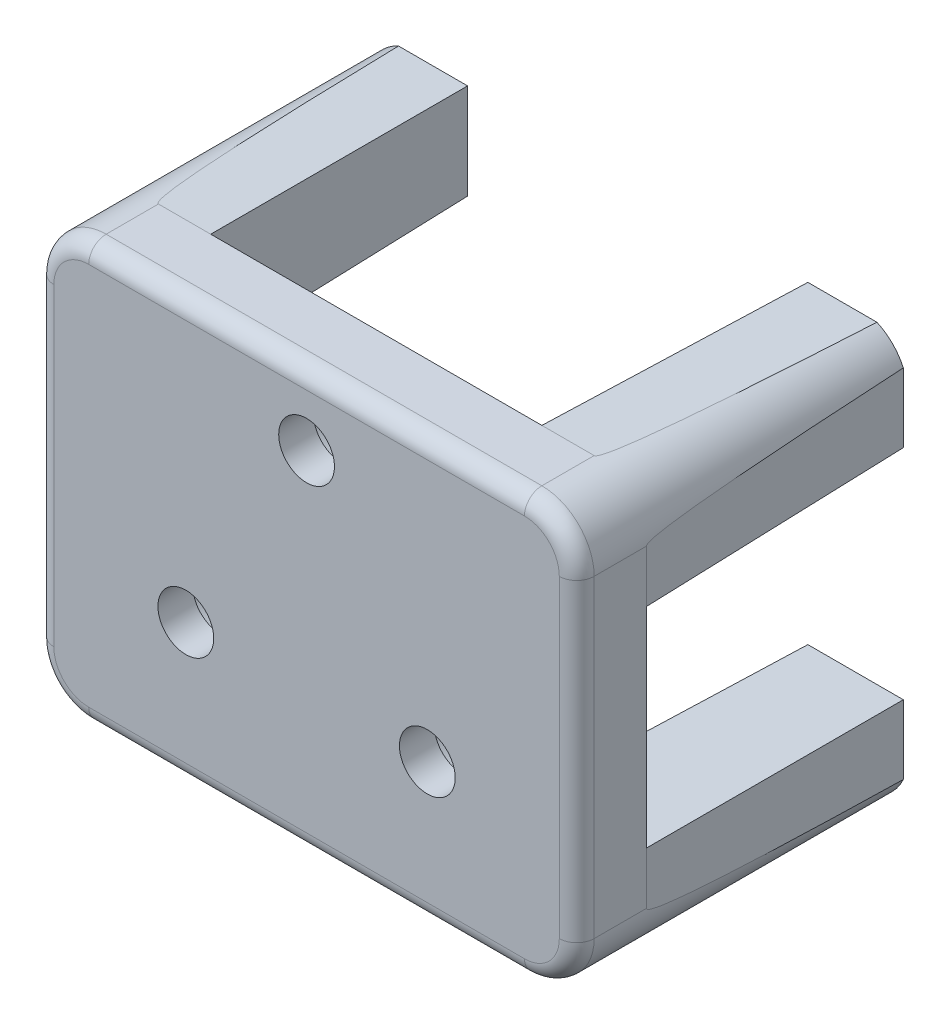
SolidWorks part; units mm, degrees
ref_plane "Front Plane" through (0, 0, 0) normal (0, 0, 1) x (1, 0, 0)
ref_plane "Top Plane" through (0, 0, 0) normal (0, 1, 0) x (1, 0, 0)
ref_plane "Right Plane" through (0, 0, 0) normal (1, 0, 0) x (0, 0, -1)
sketch "Sketch1" plane through (0, 0, 0) normal (0, 0, 1) x (1, 0, 0)
  line L1 (0, 0) -> (31, 0)
  line L2 (0, 0) -> (0, 24)
  line L3 (0, 24) -> (31, 24)
  line L4 (31, 0) -> (31, 24)
  line L5 (0, 24) -> (6, 24)
  line L6 (0, 24) -> (0, 18)
  line L7 (0, 18) -> (6, 18)
  line L8 (6, 24) -> (6, 18)
  line L9 (31, 24) -> (25, 24)
  line L10 (31, 24) -> (31, 18)
  line L11 (31, 18) -> (25, 18)
  line L12 (25, 24) -> (25, 18)
  line L13 (31, 0) -> (25, 0)
  line L14 (31, 0) -> (31, 6)
  line L15 (31, 6) -> (25, 6)
  line L16 (25, 0) -> (25, 6)
  line L17 (0, 0) -> (6, 0)
  line L18 (0, 0) -> (0, 6)
  line L19 (0, 6) -> (6, 6)
  line L20 (6, 0) -> (6, 6)
  dimension "D1" = 24
  dimension "D2" = 31
  dimension "D3" = 6
extrude "Boss-Extrude1" add sketch "Sketch1" along normal blind 4 contours L20 L1 L16 L15 L4 L11 L12 L3 L8 L7 L2 L19 | L8 L3 L2 L7 | L1 L20 L19 L2 | L3 L12 L11 L4 | L16 L1 L4 L15 region at (3, 3, 0) region at (15.5, 12, 0) region at (28, 3, 0) region at (3, 21, 0) region at (28, 21, 0)
extrude "Boss-Extrude2" add sketch "Sketch1<3>" against normal blind 15 draft 1 contours L8 L3 L2 L7 | L3 L12 L11 L4 | L16 L1 L4 L15 | L1 L20 L19 L2 region at (3, 3, 0) region at (28, 3, 0) region at (3, 21, 0) region at (28, 21, 0)
sketch "Sketch1<3>" plane through (0, 0, 0) normal (0, 0, 1) x (1, 0, 0) same geometry as "Sketch1"
sketch "Sketch2" plane through (0, 0, 0) normal (0, 0, -1) x (-1, 0, 0)
  line L0 (0, 6) -> (0, 18) construction
  line L1 (-6, 24) -> (-25, 24) construction
  line L2 (-15.5, 20) -> (-8.5718, 8) construction
  line L3 (-8.5718, 8) -> (-22.4282, 8) construction
  line L4 (-22.4282, 8) -> (-15.5, 20) construction
  line L5 (-6, 0) -> (-25, 0) construction
  circle A0 centre (-15.5, 12) radius 4 construction
  circle A1 centre (-22.4282, 8) radius 1.6
  circle A2 centre (-15.5, 20) radius 1.6
  circle A3 centre (-8.5718, 8) radius 1.6
  point P2 (-18.9641, 14)
  point P5 (0, 12)
  point P8 (-15.5, 24)
  point P12 (-12.0359, 14)
  point P13 (-15.5, 8)
  dimension "D1" = 8
  dimension "D2" = 3.2
extrude "Cut-Extrude1" cut sketch "Sketch2" against normal through all
sketch "Sketch3" plane through (0, 0, 0) normal (0, 0, -1) x (-1, 0, 0)
  circle A0 centre (-15.5, 20) radius 3
  circle A1 centre (-8.5718, 8) radius 3
  circle A2 centre (-22.4282, 8) radius 3
  dimension "D1" = 6
extrude "Cut-Extrude2" cut sketch "Sketch3" against normal blind 2
fillet "Fillet1" radius 3 4 edges at (31, 24, 2) (31, 0, 2) (0, 0, 2) (0, 24, 2) tangent propagation no
fillet "Fillet2" radius 1 8 edges at (0.8787, 0.8787, 4) (0, 12, 4) (0.8787, 23.1213, 4) (15.5, 24, 4) (30.1213, 23.1213, 4) (31, 12, 4) (30.1213, 0.8787, 4) (15.5, 0, 4)
